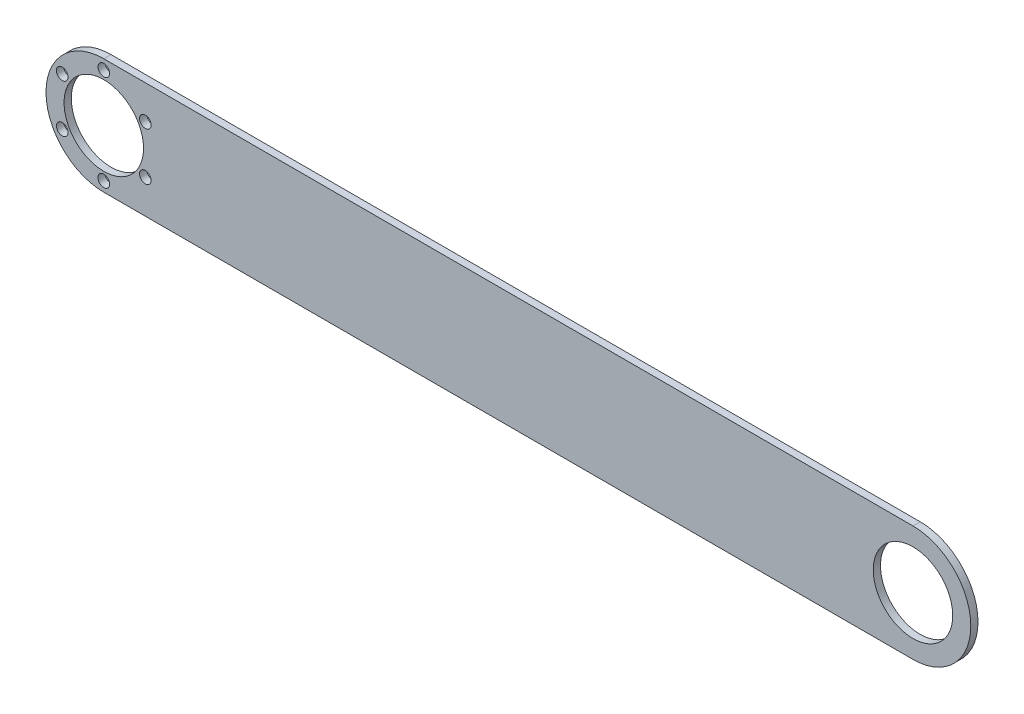
SolidWorks part; units mm, degrees
ref_plane "Front Plane" through (0, 0, 0) normal (0, 0, 1) x (1, 0, 0)
ref_plane "Top Plane" through (0, 0, 0) normal (0, 1, 0) x (1, 0, 0)
ref_plane "Right Plane" through (0, 0, 0) normal (1, 0, 0) x (0, 0, -1)
sketch "Sketch1" plane through (0, 0, 0) normal (0, 0, 1) x (1, 0, 0)
  line L1 (0, 0) -> (355.6, 0)
  line L3 (0, 50.8) -> (355.6, 50.8)
  arc A0 (0, 50.8) -> (0, 0) centre (0, 25.4) ccw
  arc A1 (355.6, 0) -> (355.6, 50.8) centre (355.6, 25.4) ccw
  point P6 (0, 0)
  point P8 (0, 0)
  dimension "D1" = 355.6
  dimension "D2" = 50.8
extrude "Boss-Extrude1" add sketch "Sketch1" along normal blind 3.175
sketch "Sketch2" plane through (0, 0, 3.175) normal (0, 0, 1) x (1, 0, 0)
  circle A0 centre (0, 25.4) radius 17.4625
  arc A1 (0, 50.8) -> (0, 0) centre (0, 25.4) ccw construction
  circle A3 centre (355.6, 25.4) radius 17.4625
  arc A5 (355.6, 0) -> (355.6, 50.8) centre (355.6, 25.4) ccw construction
  point P8 (0, 0)
  point P13 (0, 0)
  dimension "D1" = 34.925
  dimension "D2" = 34.925
extrude "Cut-Extrude1" cut sketch "Sketch2" against normal through all
sketch "Sketch4" plane through (0, 0, 3.175) normal (0, 0, 1) x (1, 0, 0)
  point P0 (0, 46.482)
  point P1 (0, 0)
  point P4 (0, 25.4)
  point P5 (18.2575, 35.941)
  point P7 (18.2575, 14.859)
  point P8 (0, 4.318)
  point P9 (-18.2575, 14.859)
  point P10 (-18.2575, 35.941)
  point P11 (0, 25.4)
  dimension "D1" = 21.082
  dimension "D2" = 6
hole_wizard "#10 Clearance Hole1" positions "3DSketch2" profile "Sketch5" hole size "#10" standard "ANSI Inch" end condition through all
sketch3d "3DSketch2"
  point P0 (18.2575, 35.941, 3.175)
  point P3 (18.2575, 14.859, 3.175)
  point P6 (0, 4.318, 3.175)
  point P9 (-18.2575, 14.859, 3.175)
  point P12 (-18.2575, 35.941, 3.175)
  point P15 (0, 46.482, 3.175)
sketch "Sketch5" plane through (18.2575, 35.941, 3.175) normal (1, 0, 0) x (0, -1, 0)
  line L0 (0, 0) -> (0, 3.175)
  line L1 (0, 3.175) -> (2.5527, 3.175)
  line L2 (2.5527, 3.175) -> (2.5527, 0)
  line L5 (2.5527, 0) -> (0, 0)
  line L11 (0, -6.35) -> (0, 107.95) construction
  dimension "Thru Hole Dia." = 5.1054
  dimension "Thru Hole Depth" = 3.175
ref_axis "Axis1" through (177.8, 50.8, 0) along (0, -0.9981, 0.0624)
ref_plane "Plane1" through (177.8, 0, 0) normal (1, 0, 0) x (0, 0, -1)
